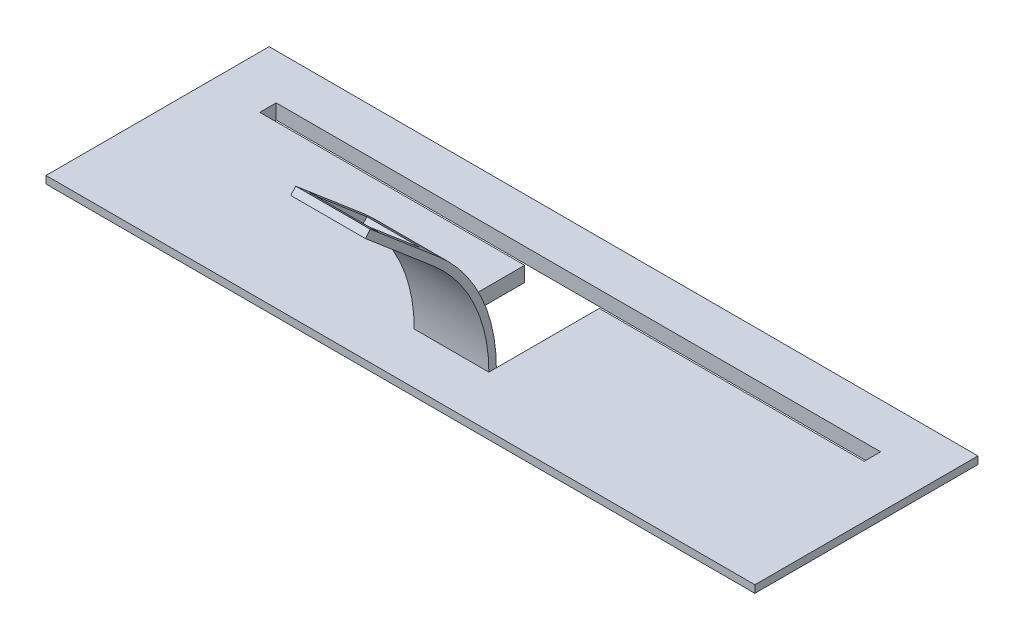
SolidWorks part; units mm, degrees
ref_plane "Front" through (0, 0, 0) normal (0, 0, 1) x (1, 0, 0)
ref_plane "Top" through (0, 0, 0) normal (0, 1, 0) x (1, 0, 0)
ref_plane "Right" through (0, 0, 0) normal (1, 0, 0) x (0, 0, -1)
sketch "Sketch1" plane through (0, 0, 0) normal (0, 1, 0) x (1, 0, 0)
  line L1 (-117.475, 34.798) -> (117.475, 34.798)
  line L2 (-117.475, 34.798) -> (-117.475, -34.798)
  line L3 (-117.475, -34.798) -> (117.475, -34.798)
  line L4 (117.475, 34.798) -> (117.475, -34.798)
  line L5 (-117.475, 34.798) -> (117.475, -34.798) construction
  line L6 (-117.475, -34.798) -> (117.475, 34.798) construction
  point P0 (0, 0)
  dimension "D1" = 69.596
  dimension "D2" = 234.95
extrude "Boss-Extrude1" add sketch "Sketch1" along normal blind 2.54
sketch "Sketch2" plane through (0, 2.54, 0) normal (0, 1, 0) x (1, 0, 0)
  line L8 (120.65, -37.973) -> (120.65, 37.973)
  line L9 (120.65, 37.973) -> (-120.65, 37.973)
  line L10 (-120.65, 37.973) -> (-120.65, -37.973)
  line L11 (-120.65, -37.973) -> (120.65, -37.973)
  line L12 (120.65, -37.973) -> (120.65, 37.973)
  line L13 (120.65, 37.973) -> (-120.65, 37.973)
  line L14 (-120.65, 37.973) -> (-120.65, -37.973)
  line L15 (-120.65, -37.973) -> (120.65, -37.973)
  dimension "D1" = 3.175
extrude "Boss-Extrude2" add sketch "Sketch2" along normal blind 2.54
sketch "Sketch3" plane through (0, 5.08, 0) normal (0, 1, 0) x (1, 0, 0)
  line L1 (-102.87, 22.606) -> (102.87, 22.606)
  line L2 (-102.87, 22.606) -> (-102.87, 12.446)
  line L3 (-102.87, 12.446) -> (102.87, 12.446)
  line L4 (102.87, 22.606) -> (102.87, 12.446)
  line L5 (120.65, 37.973) -> (-120.65, 37.973) construction
  line L6 (-12.7, 17.018) -> (-12.7, 12.446)
  line L7 (-102.87, 17.018) -> (102.87, 17.018)
  line L8 (-102.87, 17.018) -> (-102.87, 22.606)
  line L9 (-102.87, 22.606) -> (102.87, 22.606)
  line L10 (102.87, 17.018) -> (102.87, 22.606)
  line L11 (-12.7, 12.446) -> (12.7, 12.446)
  line L12 (-12.7, 12.446) -> (-12.7, -18.034)
  line L13 (0, -31.2408) -> (0, 31.2408) construction
  line L14 (12.7, 17.018) -> (12.7, 12.446)
  line L15 (-12.7, -18.034) -> (12.7, -18.034)
  line L16 (12.7, 12.446) -> (12.7, -18.034)
  point P0 (0, 0)
  point P8 (0, 0)
  dimension "D1" = 205.74
  dimension "D2" = 10.16
  dimension "D3" = 15.367
  dimension "D4" = 25.4
  dimension "D5" = 4.572
  dimension "D6" = 30.48
extrude "Cut-Extrude2" cut sketch "Sketch3" against normal through all contours L2 L7 L4 L1 | L14 L7 L6 L3 | L16 L3 L12 L15 region at (0, 5.08, -19.812) region at (0, 5.08, -14.732) region at (0, 5.08, 2.794)
sketch "Sketch4" plane through (0, 0, 0) normal (1, 0, 0) x (0, 0, -1)
  line L0 (22.606, 5.08) -> (17.018, 5.08) construction
  line L1 (22.606, 5.08) -> (17.018, 5.08)
  line L2 (-37.7211, 47.6552) -> (-39.3663, 45.72)
  line L4 (-37.973, 2.54) -> (37.973, 2.54)
  line L5 (37.973, 2.54) -> (37.973, 5.08)
  line L6 (37.973, 5.08) -> (-37.973, 5.08)
  line L7 (-37.973, 5.08) -> (-37.973, 2.54)
  line L8 (-37.973, 2.54) -> (37.973, 2.54)
  line L9 (37.973, 2.54) -> (37.973, 5.08)
  line L10 (37.973, 5.08) -> (-37.973, 5.08)
  line L11 (-37.973, 5.08) -> (-37.973, 2.54)
  line L14 (17.018, 5.08) -> (-18.034, 5.08)
  line L15 (-18.034, 5.08) -> (-18.034, 0)
  line L16 (-18.034, 0) -> (17.018, 0)
  line L17 (17.018, 0) -> (17.018, 5.08)
  line L18 (17.018, 5.08) -> (-18.034, 5.08)
  line L20 (-18.034, 0) -> (17.018, 0)
  line L21 (17.018, 0) -> (17.018, 5.08)
  line L23 (-18.034, 5.08) -> (-18.034, 0)
  arc A0 (-18.034, 5.08) -> (-37.7211, 47.6552) centre (-73.914, 5.08) ccw
  arc A1 (-20.574, 5.08) -> (-39.3663, 45.72) centre (-73.914, 5.08) ccw
  dimension "2" = 53.34
  dimension "D5" = 40.64
  dimension "D1" = 0
  dimension "D2" = 0
  dimension "D3" = 2.54
extrude "Boss-Extrude7" add sketch "Sketch4" along normal blind 12.7 and the other way blind 12.7 contours A1 L10 A0 L2 region at (0, 5.5562, 19.304)
sketch "Sketch5" plane through (0, 38.606, 45.4139) normal (0, 0.6477, 0.7619) x (1, 0, 0)
  line L4 (-12.7, 9.3372) -> (12.7, 9.3372)
  line L5 (12.7, 9.3372) -> (12.7, 11.8772)
  line L6 (12.7, 11.8772) -> (-12.7, 11.8772)
  line L7 (-12.7, 11.8772) -> (-12.7, 9.3372)
  line L8 (-12.7, 9.3372) -> (12.7, 9.3372)
  line L9 (12.7, 9.3372) -> (12.7, 11.8772)
  line L10 (12.7, 11.8772) -> (-12.7, 11.8772)
  line L11 (-12.7, 11.8772) -> (-12.7, 9.3372)
  dimension "D1" = 0
extrude "Boss-Extrude8" add sketch "Sketch5" along normal blind 30.48
sketch "Sketch6" plane through (0, 9.0493, -7.6927) normal (0, 0.7619, -0.6477) x (1, 0, 0)
  line L0 (0, -31.2408) -> (0, 31.2408) construction
  line L1 (-9.144, -62.9463) -> (9.144, -62.9463)
  line L2 (-9.144, -62.9463) -> (-9.144, -85.9651)
  line L3 (-9.144, -85.9651) -> (9.144, -85.9651)
  line L4 (12.7, -59.6057) -> (-12.7, -59.6057)
  line L5 (-12.7, -59.6057) -> (-12.7, -90.0857)
  line L6 (-12.7, -90.0857) -> (12.7, -90.0857)
  line L7 (12.7, -90.0857) -> (12.7, -59.6057)
  line L8 (12.7, -59.6057) -> (-12.7, -59.6057)
  line L9 (-12.7, -59.6057) -> (-12.7, -90.0857)
  line L10 (-12.7, -90.0857) -> (12.7, -90.0857)
  line L11 (12.7, -90.0857) -> (12.7, -59.6057)
  line L12 (9.144, -62.9463) -> (9.144, -85.9651)
  line L13 (-9.144, -62.9463) -> (9.144, -85.9651) construction
  line L14 (-9.144, -85.9651) -> (9.144, -62.9463) construction
  point P2 (0, -74.4557)
  point P11 (0, -75.5479)
  point P12 (0, -74.4557)
  dimension "D2" = 18.288
  dimension "D3" = 23.0188
  dimension "D1" = 0
extrude "Cut-Extrude3" cut sketch "Sketch6" against normal up to next contours L12 L1 L2 L3 region at (0, 57.2734, 49.0354)
sketch "Sketch9" plane through (0, 9.0493, -7.6927) normal (0, 0.7619, -0.6477) x (1, 0, 0)
  line L0 (0, -31.2408) -> (0, 31.2408) construction
  line L2 (-9.144, -62.9463) -> (9.144, -62.9463) construction
  circle A0 centre (-10.3187, -85.1713) radius 1
  circle A1 centre (10.3187, -85.1713) radius 1
  dimension "D3" = 2
  dimension "D1" = 22.225
  dimension "D2" = 20.6375
extrude "Cut-Extrude4" cut sketch "Sketch9" against normal up to next
